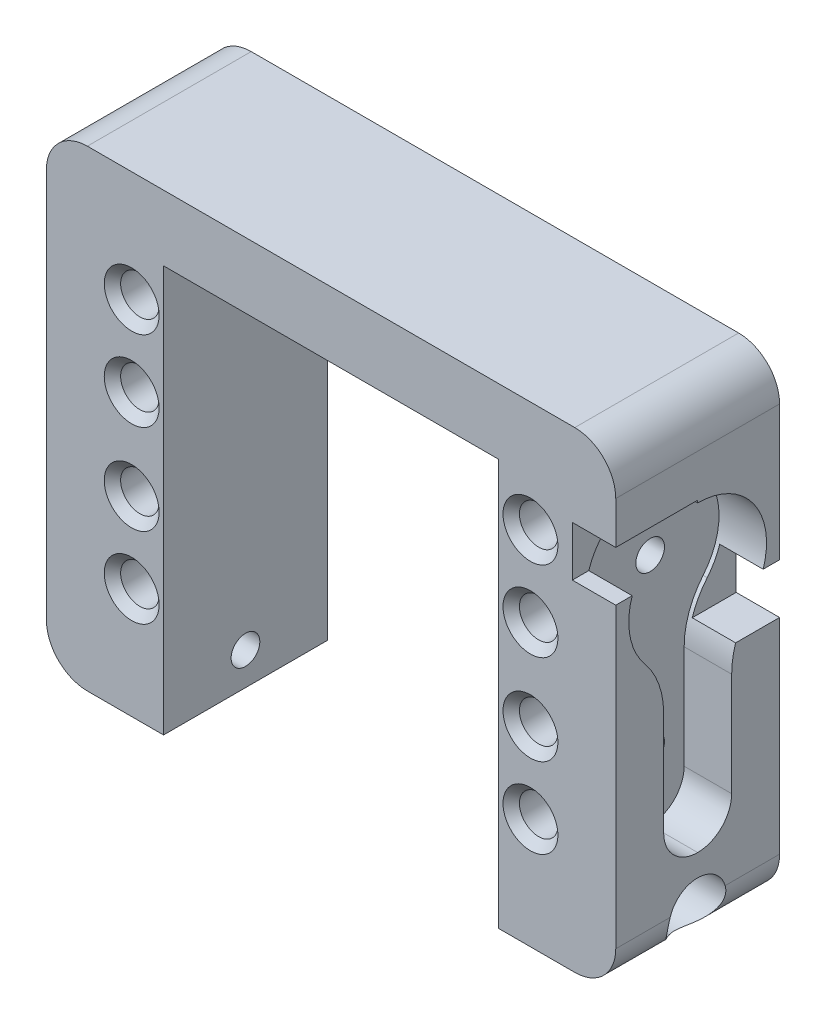
SolidWorks part; units mm, degrees
material "ABS"
ref_plane "Front Plane" through (0, 0, 0) normal (0, 0, 1) x (1, 0, 0)
ref_plane "Top Plane" through (0, 0, 0) normal (0, 1, 0) x (1, 0, 0)
ref_plane "Right Plane" through (0, 0, 0) normal (1, 0, 0) x (0, 0, -1)
sketch "Sketch1" plane through (0, 0, 0) normal (1, 0, 0) x (0, 0, -1)
  line L1 (-10, 10) -> (10, 10)
  line L2 (-10, 10) -> (-10, -10)
  line L3 (-10, -10) -> (10, -10)
  line L4 (10, 10) -> (10, -10)
  line L5 (-10, 10) -> (10, -10) construction
  line L6 (-10, -10) -> (10, 10) construction
  point P0 (0, 0)
  dimension "D1" = 20
  dimension "D2" = 20
extrude "Boss-Extrude1" add sketch "Sketch1" along normal blind 20
sketch "Sketch2" plane through (20, 0, 0) normal (1, 0, 0) x (0, 0, -1)
  line L1 (-10, 35) -> (10, 35)
  line L2 (-10, 35) -> (-10, -35)
  line L3 (-10, -35) -> (10, -35)
  line L4 (10, 35) -> (10, -35)
  line L5 (-10, 35) -> (10, -35) construction
  line L6 (-10, -35) -> (10, 35) construction
  point P0 (0, 0)
  dimension "D1" = 20
  dimension "D2" = 70
extrude "Boss-Extrude2" add sketch "Sketch2" along normal blind 10.3
sketch "Sketch4" plane through (30.3, 0, 0) normal (1, 0, 0) x (0, 0, -1)
  line L0 (0, 7.65) -> (0, 8.1702) construction
  line L1 (7.65, 7.65) -> (-7.65, 7.65) construction
  line L17 (4.15, -26.55) -> (-4.15, -26.55) construction
  line L18 (-7.65, 7.65) -> (7.65, 7.65) construction
  line L22 (-7.65, 7.65) -> (-7.65, -27.55) construction
  line L23 (-7.65, -27.55) -> (7.65, -27.55) construction
  line L24 (7.65, 7.65) -> (7.65, -27.55) construction
  line L25 (-7.65, 7.65) -> (7.65, -27.55) construction
  line L26 (-7.65, -27.55) -> (7.65, 7.65) construction
  line L27 (4.15, -26.55) -> (4.15, -28.55) construction
  line L28 (4.15, -28.55) -> (-4.15, -28.55) construction
  line L29 (-4.15, -26.55) -> (-4.15, -28.55) construction
  line L30 (4.15, -26.55) -> (-4.15, -28.55) construction
  line L31 (4.15, -28.55) -> (-4.15, -26.55) construction
  line L34 (4.15, -28.55) -> (-4.15, -28.55)
  line L35 (-4.15, -28.55) -> (-4.15, -7.3118)
  line L36 (4.15, -28.55) -> (4.15, -7.3118)
  arc A1 (4.15, -6.4265) -> (-4.15, -6.4265) centre (0, 0) ccw construction
  arc A2 (4.15, -7.3118) -> (-4.15, -7.3118) centre (0, 0) ccw
  point P1 (0, -27.55)
  point P7 (0, -13.75)
  point P10 (0, 7.65)
  point P14 (0, -9.95)
  dimension "D1" = 15.3
  dimension "D5" = 2
  dimension "D2" = 15.3
  dimension "D3" = 35.2
  dimension "D4" = 8.3
extrude "Cut-Extrude1" cut sketch "Sketch4" against normal blind 5.8
fillet "Fillet1" radius 4.15 2 edges at (27.4, -28.55, 4.15) (27.4, -28.55, -4.15)
fillet "Fillet2" radius 10 2 edges at (27.4, -7.3118, 4.15) (27.4, -7.3118, -4.15)
sketch "Sketch5" plane through (0, 0, 0) normal (-1, 0, 0) x (0, 0, 1)
  circle A0 centre (0, 0) radius 1.75
  dimension "D1" = 3.5
extrude "Cut-Extrude2" cut sketch "Sketch5" against normal through all
sketch "Sketch6" plane through (24.5, 0, 0) normal (1, 0, 0) x (0, 0, -1)
  line L0 (0, -19.35) -> (0, 0) construction
  line L1 (0, -25.65) -> (0, -23.15) construction
  line L2 (0, -23.15) -> (0, -21.85) construction
  line L3 (0, -21.85) -> (0, -19.35) construction
  line L5 (0, 0) -> (1.164, 0) construction
  line L6 (0, 0) -> (0, -9.35) construction
  line L7 (0, -9.35) -> (1.164, -9.35) construction
  line L8 (1.164, 0) -> (1.164, -9.35) construction
  line L9 (0, 0) -> (1.164, -9.35) construction
  line L10 (0, -9.35) -> (1.164, 0) construction
  circle A0 centre (0, -20.6) radius 1.75
  circle A1 centre (0, -9.35) radius 1.75 construction
  point P11 (0.582, -4.675)
  dimension "D5" = 3.5
  dimension "D6" = 9.35
  dimension "D7" = 3.5
  dimension "D1" = 19.35
  dimension "D2" = 2.5
  dimension "D3" = 1.3
  dimension "D4" = 2.5
extrude "Cut-Extrude3" cut sketch "Sketch6" against normal up to next
sketch "Sketch13" plane through (0, 0, 0) normal (-1, 0, 0) x (0, 0, 1)
  line L1 (-10, 10) -> (10, 10)
  line L2 (-10, 10) -> (-10, -10)
  line L3 (-10, -10) -> (10, -10)
  line L4 (10, 10) -> (10, -10)
extrude "Cut-Extrude9" cut sketch "Sketch13" against normal up to surface (20 mm away) up to face at (20, 22.5, 0)
sketch "Sketch29" plane through (30.3, 0, 0) normal (1, 0, 0) x (0, 0, -1)
  line L0 (0, 0) -> (0, 2.6) construction
  line L1 (15.1094, -8.7) -> (15.1094, -2.6)
  line L2 (0, 2.6) -> (-15.1094, 2.6)
  line L4 (0, 2.6) -> (0, 3.8)
  line L5 (0, 3.8) -> (0, 7.5)
  line L6 (0, 7.5) -> (0, 8.7)
  line L7 (0, 8.7) -> (-15.1094, 8.7)
  line L8 (-15.1094, 8.7) -> (-15.1094, 2.6)
  line L9 (0, -2.6) -> (15.1094, -2.6)
  line L10 (0, -2.6) -> (0, -3.8)
  line L11 (0, -3.8) -> (0, -7.5)
  line L12 (0, -7.5) -> (0, -8.7)
  line L13 (0, -8.7) -> (15.1094, -8.7)
  point P19 (0, 0)
  dimension "D1" = 2.6
  dimension "D2" = 1.2
  dimension "D3" = 3.7
  dimension "D4" = 1.2
  dimension "D5" = 2
extrude "Cut-Extrude18" cut sketch "Sketch29" against normal blind 5.3
sketch "Sketch32" plane through (30.3, 0, 0) normal (1, 0, 0) x (0, 0, -1)
  line L0 (0, -28.55) -> (0, -38.725) construction
  line L1 (10, -35) -> (10, -8.7) construction
  line L2 (-10, -35) -> (10, -35)
  line L3 (-10, -35) -> (-10, -38.725)
  line L4 (-10, -38.725) -> (10, -38.725)
  line L5 (10, -35) -> (10, -38.725)
  dimension "D1" = 10.175
extrude "Boss-Extrude3" add sketch "Sketch32" against normal up to surface (10.3 mm away) up to face at (20, 0, 0)
sketch "Sketch31" plane through (30.3, 0, 0) normal (1, 0, 0) x (0, 0, -1)
  line L2 (0, 8.7) -> (0, 18.875) construction
  line L3 (10, -2.6) -> (10, 35) construction
  line L4 (-10, 35) -> (10, 35)
  line L5 (-10, 35) -> (-10, 18.875)
  line L6 (-10, 18.875) -> (10, 18.875)
  line L7 (10, 35) -> (10, 18.875)
  dimension "D1" = 10.175
extrude "Cut-Extrude19" cut sketch "Sketch31" against normal through all
sketch "Sketch34" plane through (20, 0, 0) normal (-1, 0, 0) x (0, 0, 1)
  line L4 (10, -38.725) -> (10, 18.875)
  line L5 (10, 18.875) -> (-10, 18.875)
  line L6 (-10, 18.875) -> (-10, -38.725)
  line L7 (-10, -38.725) -> (10, -38.725)
  line L8 (10, -38.725) -> (10, 18.875)
  line L9 (10, 18.875) -> (-10, 18.875)
  line L10 (-10, 18.875) -> (-10, -38.725)
  line L11 (-10, -38.725) -> (10, -38.725)
  circle A0 centre (0, -20.6) radius 1.75 construction
  circle A1 centre (0, 0) radius 1.75 construction
  circle A2 centre (0, -20.6) radius 1.75
  circle A3 centre (0, 0) radius 1.75
  dimension "D1" = 0
extrude "Boss-Extrude5" add sketch "Sketch34" along normal blind 4
sketch "Sketch35" plane through (16, 0, 0) normal (-1, 0, 0) x (0, 0, 1)
  line L0 (10, -38.725) -> (10, 18.875) construction
  line L1 (-10, 18.875) -> (10, 18.875)
  line L2 (-10, 18.875) -> (-10, 10.875)
  line L3 (-10, 10.875) -> (10, 10.875)
  line L4 (10, 18.875) -> (10, 10.875)
  line L5 (0, 10.875) -> (0, -30.725) construction
  line L6 (-10, -38.725) -> (10, -38.725) construction
  line L7 (-10, -38.725) -> (-10, -30.725) construction
  line L8 (-10, -30.725) -> (10, -30.725) construction
  line L9 (10, -38.725) -> (10, -30.725) construction
  dimension "D1" = 41.6
extrude "Boss-Extrude6" add sketch "Sketch35" along normal blind 40.9
sketch "Sketch37" plane through (-24.9, 0, 0) normal (-1, 0, 0) x (0, 0, 1)
  line L1 (-10, 18.875) -> (10, 18.875)
  line L2 (-10, 18.875) -> (-10, -38.725)
  line L3 (-10, -38.725) -> (10, -38.725)
  line L4 (10, 18.875) -> (10, -38.725)
extrude "Boss-Extrude7" add sketch "Sketch37" along normal blind 14.3
sketch "Sketch38" plane through (0, 0, 10) normal (0, 0, 1) x (1, 0, 0)
  line L0 (-24.9, 10.875) -> (-24.9, -9.925) construction
  line L1 (-24.9, -9.925) -> (-24.9, -30.725) construction
  line L2 (-24.9, -38.725) -> (-24.9, 10.875) construction
  line L3 (-24.9, -9.925) -> (-39.2, -9.925) construction
  line L4 (-39.2, -38.725) -> (-39.2, 18.875) construction
  line L5 (-24.9, 0.475) -> (-28.79, 0.475) construction
  line L6 (-28.79, 0.475) -> (-28.79, 5.375) construction
  line L7 (-24.9, 10.875) -> (16, 10.875) construction
  line L8 (-4.45, 10.875) -> (-4.45, -38.725) construction
  line L9 (-24.9, -38.725) -> (-4.45, -38.725) construction
  circle A0 centre (-28.79, 5.375) radius 2.35
  circle A1 centre (-28.79, -4.425) radius 2.35
  circle A2 centre (-28.79, -25.225) radius 2.35
  circle A3 centre (-28.79, -15.425) radius 2.35
  circle A4 centre (19.89, 5.375) radius 2.35
  circle A5 centre (19.89, -4.425) radius 2.35
  circle A6 centre (19.89, -15.425) radius 2.35
  circle A7 centre (19.89, -25.225) radius 2.35
  dimension "D4" = 4.7
  dimension "D1" = 41.6
  dimension "D2" = 3.89
  dimension "D3" = 4.9
extrude "Cut-Extrude20" cut sketch "Sketch38" against normal blind 8
chamfer "Chamfer1" distance 1 angle 45 8 edges at (22.24, -25.225, 10) (17.54, -15.425, 10) (22.24, -4.425, 10) (17.54, 5.375, 10) (-26.44, 5.375, 10) (-26.44, -15.425, 10) (-31.14, -25.225, 10) (-31.14, -4.425, 10)
fillet "Fillet3" radius 5 2 edges at (30.3, 18.875, 0) (-39.2, 18.875, 0)
sketch "Sketch41" plane through (16, 0, 0) normal (-1, 0, 0) x (0, 0, 1)
  circle A0 centre (0, 0) radius 3.5
  circle A1 centre (0, -20.6) radius 3.5
  dimension "D1" = 7
  dimension "D2" = 7
extrude "Cut-Extrude23" cut sketch "Sketch41" against normal blind 2.5
sketch "Sketch45" plane through (30.3, 0, 0) normal (1, 0, 0) x (0, 0, -1)
  line L0 (0, -38.725) -> (0, -34.725) construction
  line L2 (-10, -38.725) -> (10, -38.725) construction
  line L3 (0, -34.725) -> (0, -28.55) construction
  circle A0 centre (0, -34.725) radius 1.75
  dimension "D1" = 3.5
  dimension "D2" = 4
extrude "Cut-Extrude27" cut sketch "Sketch45" against normal through all
sketch "Sketch46" plane through (-39.2, 0, 0) normal (-1, 0, 0) x (0, 0, 1)
  circle A0 centre (0, -34.725) radius 3.5
  dimension "D1" = 7
extrude "Cut-Extrude28" cut sketch "Sketch46" against normal blind 11
sketch "Sketch47" plane through (30.3, 0, 0) normal (1, 0, 0) x (0, 0, -1)
  circle A0 centre (0, -34.725) radius 3.5
  dimension "D1" = 7
extrude "Cut-Extrude29" cut sketch "Sketch47" against normal blind 11
fillet "Fillet5" radius 5 2 edges at (30.3, -38.725, 0) (-39.2, -38.725, 0)
mirror "Mirror1" [suppressed] of bodies 167
delete or keep bodies "Body-Delete/Keep 1" [suppressed] type delete bodies bodies 167
